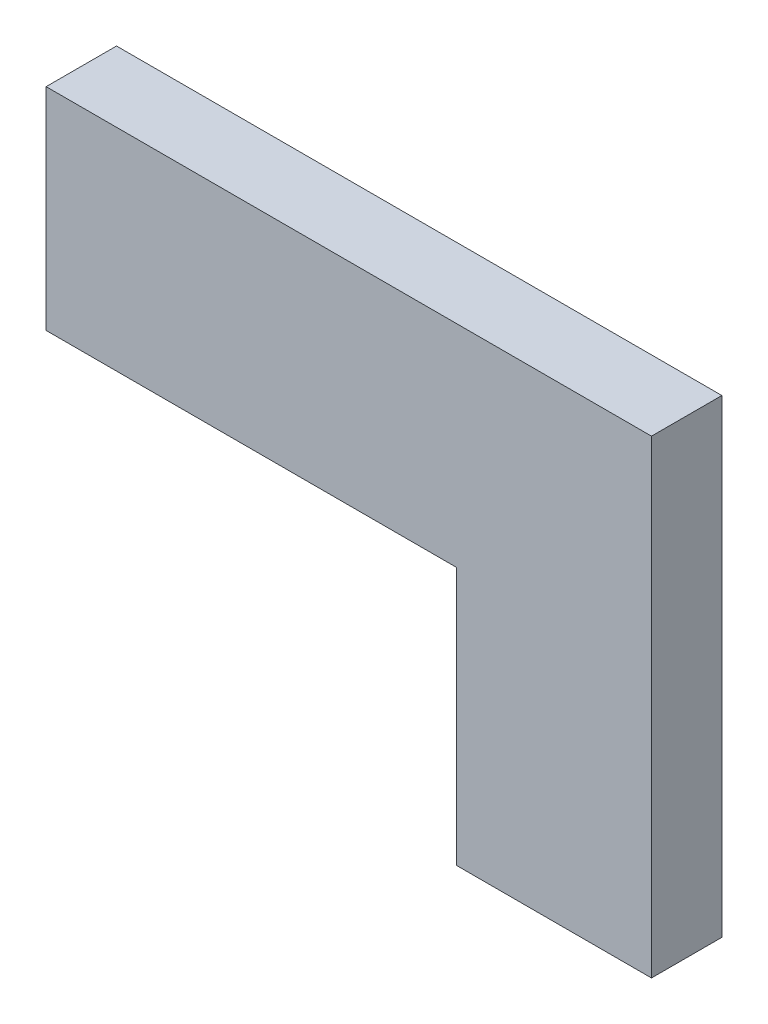
SolidWorks part; units mm, degrees
ref_plane "Front Plane" through (0, 0, 0) normal (0, 0, 1) x (1, 0, 0)
ref_plane "Top Plane" through (0, 0, 0) normal (0, 1, 0) x (1, 0, 0)
ref_plane "Right Plane" through (0, 0, 0) normal (1, 0, 0) x (0, 0, -1)
sketch "Sketch1" plane through (0, 0, 0) normal (0, 0, 1) x (1, 0, 0)
  line L1 (-2.5, 202.5) -> (255.5, 202.5)
  line L2 (-2.5, 202.5) -> (-2.5, 112.5)
  line L3 (-2.5, 112.5) -> (172.5, 112.5)
  line L6 (255.5, 2.5) -> (172.5, 2.5)
  line L7 (255.5, 2.5) -> (255.5, 202.5)
  line L9 (172.5, 2.5) -> (172.5, 112.5)
  dimension "D1" = 110
  dimension "D2" = 175
extrude "Boss-Extrude1" add sketch "Sketch1" along normal up to surface (30 mm away)
equation "\"TubingShort\"=110"
equation "\"D1@Sketch1\"=\"TubingShort\""
equation "\"TubingLong\"=175"
equation "\"D2@Sketch1\"=\"TubingLong\""
equation "\"Length\"= 283"
equation "\"Width\"= 225"
equation "\"WallThickness\"= 12.5"
equation "\"UpperWaterJacketThickness\"= 28"
equation "\"SpacerHeight\"= 80.2"
equation "\"PlateLength\"=252"
equation "\"PlateWidth\"=190"
equation "\"PlateHoleDiameter\"=5.9"
equation "\"PlateHoleBottom\"= 2"
equation "\"PlateHoleSide\"= 1.55"
equation "\"PlateHoleSpacing\"= 3.1"
equation "\"PlateThickness\"=1.55"
equation "\"ReservoirBottom\"=12.5"
equation "\"ReservoirSupportWidth\"=12"
equation "\"ReservoirSupportHeight\"=15.1"
equation "\"ReservoirSupportPlacementHeight\"=50"
equation "\"ReservoirHoleDiameter\"=12.7"
equation "\"ReservoirHoleRight\"= 25"
equation "\"ReservoirHoleTop\"= \"ReservoirSupportPlacementHeight\""
equation "\"ReservoirHeight\"=90"
equation "\"ReservoirPortBottom\"=4"
equation "\"ReservoirPortTop\"= 10"
equation "\"ReservoirPortWidth\"=101"
